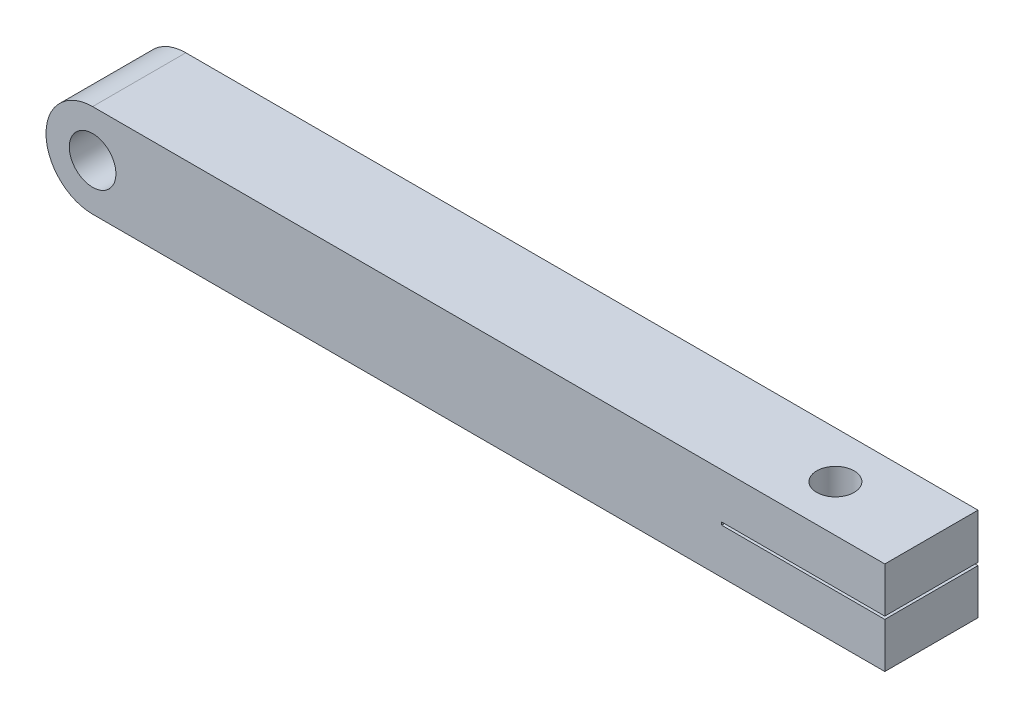
SolidWorks part; units mm, degrees
material "PET"
ref_plane "Front Plane" through (0, 0, 0) normal (0, 0, 1) x (1, 0, 0)
ref_plane "Top Plane" through (0, 0, 0) normal (0, 1, 0) x (1, 0, 0)
ref_plane "Right Plane" through (0, 0, 0) normal (1, 0, 0) x (0, 0, -1)
sketch "Sketch1" plane through (0, 0, 0) normal (0, 0, 1) x (1, 0, 0)
  line L9 (85.725, 0.1905) -> (85.725, -0.1905)
  line L11 (0, 6.35) -> (107.95, 6.35)
  line L12 (107.95, 6.35) -> (107.95, 0.1905)
  line L13 (107.95, 0.1905) -> (85.725, 0.1905)
  line L15 (0, -6.35) -> (107.95, -6.35)
  line L16 (107.95, -6.35) -> (107.95, -0.1905)
  line L18 (85.725, -0.1905) -> (107.95, -0.1905)
  circle A0 centre (0, 0) radius 3.175
  arc A9 (0, 6.35) -> (0, -6.35) centre (0, 0) ccw
  point P0 (-6.35, 0)
  point P3 (0, 0)
  point P5 (0, 0)
  point P17 (107.95, 0.1905)
  point P20 (107.95, 6.35)
  point P27 (0, 12.7)
  point P30 (0, 0)
  dimension "D6" = 6.35
  dimension "D7" = 22.225
  dimension "D1" = 114.3
  dimension "D3" = 6.35
  dimension "D4" = 12.7
  dimension "D5" = 0.381
extrude "Boss-Extrude1" add sketch "Sketch1" along normal blind 12.7
hole_wizard "#10 Clearance Hole2" positions "Sketch5" profile "Sketch6" hole size "#10" standard "ANSI Inch" end condition through all
sketch "Sketch5" plane through (0, 6.35, 0) normal (0, 1, 0) x (1, 0, 0)
  line L0 (107.95, 0) -> (0, 0) construction
  line L1 (85.725, -12.7) -> (85.725, 0) construction
  point P0 (94.869, -6.35)
  dimension "D1" = 6.35
  dimension "D2" = 9.144
sketch "Sketch6" plane through (94.869, 6.35, 6.35) normal (1, 0, 0) x (0, 0, 1)
  line L0 (0, 0) -> (0, 12.7)
  line L1 (0, 12.7) -> (2.5527, 12.7)
  line L2 (2.5527, 12.7) -> (2.5527, 0)
  line L5 (2.5527, 0) -> (0, 0)
  line L11 (0, -6.35) -> (0, 107.95) construction
  dimension "Thru Hole Dia." = 5.1054
  dimension "Thru Hole Depth" = 12.7
